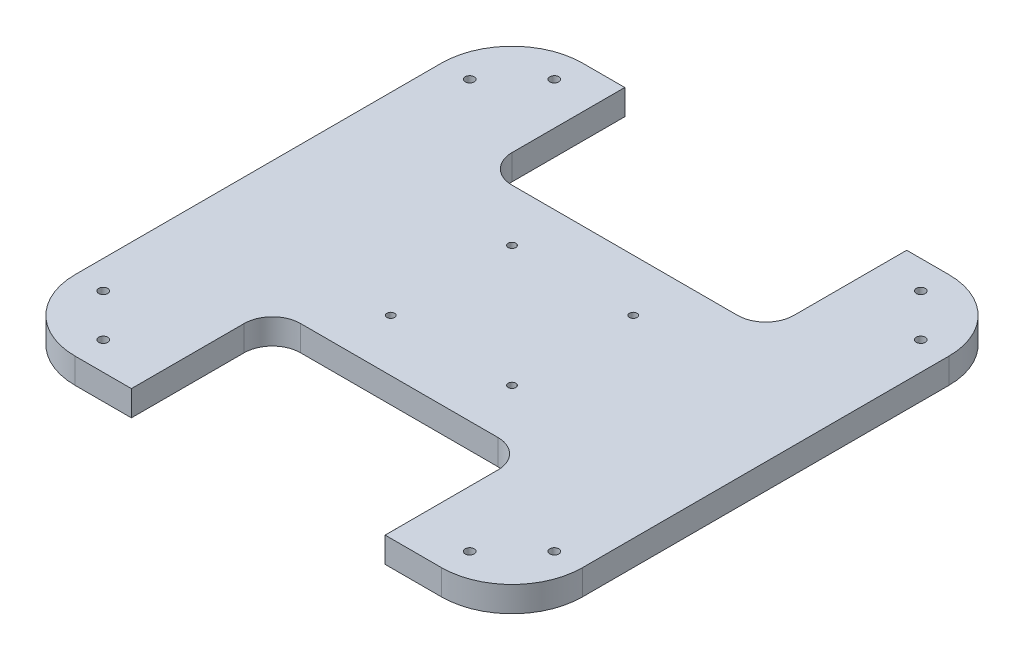
SolidWorks part; units mm, degrees
ref_plane "Front Plane" through (0, 0, 0) normal (0, 0, 1) x (1, 0, 0)
ref_plane "Top Plane" through (0, 0, 0) normal (0, 1, 0) x (1, 0, 0)
ref_plane "Right Plane" through (0, 0, 0) normal (1, 0, 0) x (0, 0, -1)
sketch "Sketch1" plane through (0, 0, 0) normal (0, 1, 0) x (1, 0, 0)
  line L1 (-65, -90) -> (65, -90)
  line L2 (-90, -65) -> (-90, 65)
  line L3 (-65, 90) -> (65, 90)
  line L4 (90, -65) -> (90, 65)
  arc A0 (-90, 65) -> (-65, 90) centre (-65, 65) cw
  arc A1 (65, 90) -> (90, 65) centre (65, 65) cw
  arc A2 (90, -65) -> (65, -90) centre (65, -65) cw
  arc A3 (-65, -90) -> (-90, -65) centre (-65, -65) cw
  point P4 (-90, 0)
  point P6 (0, 90)
  dimension "D3" = 25
  dimension "D1" = 180
  dimension "D2" = 180
extrude "Plate" add sketch "Sketch1" along normal blind 9
sketch "Sketch3" plane through (0, 9, 0) normal (0, 1, 0) x (1, 0, 0)
  line L0 (-65, 90) -> (-65, -90) construction
  line L1 (65, 90) -> (65, -90) construction
  line L2 (-90, 65) -> (90, 65) construction
  line L3 (-90, -65) -> (90, -65) construction
  circle A0 centre (-65, 80) radius 1.6
  circle A1 centre (-80, 65) radius 1.6
  circle A2 centre (80, 65) radius 1.6
  circle A3 centre (80, -65) radius 1.6
  circle A4 centre (65, 80) radius 1.6
  circle A5 centre (65, -80) radius 1.6
  circle A6 centre (-65, -80) radius 1.6
  circle A7 centre (-80, -65) radius 1.6
  dimension "D1" = 3.2
  dimension "D2" = 15
  dimension "D3" = 15
  dimension "D4" = 15
  dimension "D5" = 15
  dimension "D6" = 15
  dimension "D7" = 15
  dimension "D8" = 15
  dimension "D9" = 15
extrude "Hex Holes" cut sketch "Sketch3" against normal through all
sketch "Sketch4" plane through (0, 9, 0) normal (0, 1, 0) x (1, 0, 0)
  line L0 (-90, -65) -> (-90, 65) construction
  line L1 (-65, -90) -> (65, -90) construction
  circle A0 centre (-21.5, 21.5) radius 1.35
  circle A1 centre (21.5, 21.5) radius 1.35
  circle A2 centre (21.5, -21.5) radius 1.35
  circle A3 centre (-21.5, -21.5) radius 1.35
  dimension "D1" = 2.7
  dimension "D2" = 43
  dimension "D3" = 43
  dimension "D4" = 68.5
  dimension "D5" = 68.5
extrude "LiDAR Holes" cut sketch "Sketch4" against normal through all
sketch "Sketch5" plane through (0, 9, 0) normal (0, 1, 0) x (1, 0, 0)
  line L0 (-65, 90) -> (65, 90) construction
  line L1 (50, 90) -> (-50, 90)
  line L2 (50, 90) -> (50, 40)
  line L3 (50, 40) -> (-50, 40)
  line L4 (-50, 90) -> (-50, 40)
  line L5 (-65, -90) -> (65, -90) construction
  line L6 (45, -90) -> (-45, -90)
  line L7 (45, -90) -> (45, -40)
  line L8 (45, -40) -> (-45, -40)
  line L9 (-45, -90) -> (-45, -40)
  point P6 (0, 90)
  point P7 (0, 90)
  point P14 (0, -90)
  point P15 (0, -90)
  dimension "D1" = 100
  dimension "D2" = 50
  dimension "D3" = 50
  dimension "D4" = 90
extrude "Cut-Extrude1" cut sketch "Sketch5" against normal through all
sketch "Sketch6" plane through (0, 0, 0) normal (0, -1, 0) x (1, 0, 0)
  circle A0 centre (-21.5, 21.5) radius 3.5
  circle A1 centre (21.5, 21.5) radius 3.5
  circle A2 centre (-21.5, -21.5) radius 3.5
  circle A3 centre (21.5, -21.5) radius 3.5
  dimension "D1" = 7
extrude "Cut-Extrude2" cut sketch "Sketch6" against normal blind 5
fillet "Fillet1" radius 10 4 edges at (45, 4.5, 40) (-45, 4.5, 40) (50, 4.5, -40) (-50, 4.5, -40)
